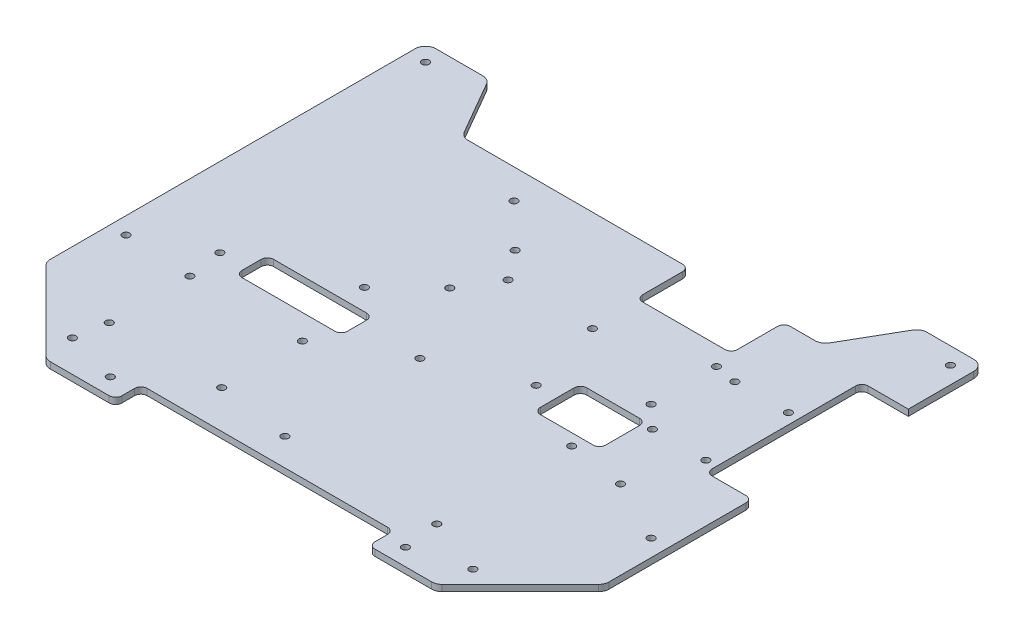
SolidWorks part; units mm, degrees
material "Acier non allié"
ref_plane "Front" through (0, 0, 0) normal (0, 0, 1) x (1, 0, 0)
ref_plane "Top" through (0, 0, 0) normal (0, 1, 0) x (1, 0, 0)
ref_plane "Right" through (0, 0, 0) normal (1, 0, 0) x (0, 0, -1)
sketch "Esquisse1" plane through (0, 0, 0) normal (0, 1, 0) x (1, 0, 0)
  line L0 (0, 0) -> (0, 190) construction
  line L1 (-92.5, 0) -> (92.5, 0)
  line L2 (92.5, 0) -> (132.5, 40)
  line L3 (132.5, 40) -> (132.5, 220)
  line L4 (132.5, 220) -> (102.5, 220)
  line L5 (102.5, 220) -> (85.1795, 190)
  line L6 (85.1795, 190) -> (-85.1795, 190)
  line L7 (-102.5, 220) -> (-85.1795, 190)
  line L8 (-132.5, 220) -> (-102.5, 220)
  line L9 (-132.5, 40) -> (-132.5, 220)
  line L10 (-92.5, 0) -> (-132.5, 40)
  dimension "D1" = 132.5
  dimension "D2" = 220
  dimension "D3" = 60
  dimension "D4" = 30
  dimension "D5" = 40
  dimension "D6" = 40
  dimension "D7" = 30
extrude "Boss.-Extru.1" add sketch "Esquisse1" along normal blind 3
fillet "Congé1" radius 5 10 edges at (92.5, 1.5, 0) (132.5, 1.5, -40) (132.5, 1.5, -220) (102.5, 1.5, -220) (85.1795, 1.5, -190) (-85.1795, 1.5, -190) (-102.5, 1.5, -220) (-132.5, 1.5, -220) (-92.5, 1.5, 0) (-132.5, 1.5, -40)
sketch "Esquisse2" plane through (0, 3, 0) normal (0, 1, 0) x (1, 0, 0)
  line L0 (0, 0) -> (0, 294.1173) construction
  line L2 (-90.4289, 0) -> (90.4289, 0) construction
  circle A0 centre (70, 8) radius 1
  circle A1 centre (124.5, 70) radius 1
  circle A2 centre (124.5, 212) radius 1
  circle A3 centre (-124.5, 212) radius 1
  circle A4 centre (-124.5, 70) radius 1
  circle A5 centre (-70, 8) radius 1
  dimension "D2" = 2
  dimension "D6" = 2
  dimension "D9" = 2
  dimension "D1" = 70
  dimension "D3" = 8
  dimension "D4" = 124.5
  dimension "D5" = 70
  dimension "D7" = 124.5
  dimension "D8" = 212
extrude "Enlèv. mat.-Extru.1" cut sketch "Esquisse2" against normal blind 3
hole_wizard "Dégagement M31" positions "Esquisse3" profile "Esquisse4" hole size "M3" standard "ISO" end condition through all
sketch "Esquisse3" plane through (0, 3, 0) normal (0, 1, 0) x (1, 0, 0)
  point P0 (70, 8)
  point P3 (-70, 8)
  point P6 (-124.5, 70)
  point P9 (-124.5, 212)
  point P12 (124.5, 212)
  point P15 (124.5, 70)
sketch "Esquisse4" plane through (70, 3, -8) normal (1, 0, 0) x (0, 0, 1)
  line L0 (0, 0) -> (0, 3)
  line L1 (0, 3) -> (1.7, 3)
  line L2 (1.7, 3) -> (1.7, 0)
  line L5 (1.7, 0) -> (0, 0)
  line L11 (0, -6.35) -> (0, 107.95) construction
  dimension "Diamètre du perçage jusqu'au prochain" = 3.4
  dimension "Profondeur du perçage jusqu'au prochain" = 3
sketch "Esquisse5" plane through (0, 3, 0) normal (0, 1, 0) x (1, 0, 0)
  line L0 (82.2927, 190) -> (-82.2927, 190) construction
  line L1 (67.5, 190) -> (22.5, 190)
  line L2 (67.5, 190) -> (67.5, 165)
  line L3 (67.5, 165) -> (22.5, 165)
  line L4 (22.5, 190) -> (22.5, 165)
  line L5 (132.5, 42.0711) -> (132.5, 215) construction
  line L6 (132.5, 184) -> (110.5, 184)
  line L7 (132.5, 184) -> (132.5, 110)
  line L8 (132.5, 110) -> (110.5, 110)
  line L9 (110.5, 184) -> (110.5, 110)
  line L10 (127.5, 220) -> (105.3868, 220) construction
  dimension "D1" = 25
  dimension "D2" = 65
  dimension "D3" = 110
  dimension "D4" = 36
  dimension "D5" = 110
  dimension "D6" = 22
extrude "Enlèv. mat.-Extru.2" cut sketch "Esquisse5" against normal through all
fillet "Congé2" radius 3 7 edges at (132.5, 1.5, -110) (110.5, 1.5, -110) (110.5, 1.5, -184) (67.5, 1.5, -190) (67.5, 1.5, -165) (22.5, 1.5, -165) (22.5, 1.5, -190)
sketch "Esquisse6" plane through (0, 3, 0) normal (0, 1, 0) x (1, 0, 0)
  line L0 (110.5, 140.5) -> (-167.6757, 140.5) construction
  line L1 (110.5, 181) -> (110.5, 113) construction
  line L2 (-90.4289, 0) -> (90.4289, 0) construction
  line L3 (110.5, 181) -> (110.5, 113) construction
  circle A0 centre (69.5, 156) radius 1
  circle A1 centre (-26, 156) radius 1
  circle A2 centre (-46.5, 176) radius 1
  circle A3 centre (69.5, 125) radius 1
  circle A4 centre (-26, 125) radius 1
  circle A5 centre (-46.5, 105) radius 1
  dimension "D4" = 2
  dimension "D6" = 2
  dimension "D10" = 2
  dimension "D1" = 140.5
  dimension "D2" = 41
  dimension "D3" = 15.5
  dimension "D5" = 136.5
  dimension "D7" = 15.5
  dimension "D8" = 35.5
  dimension "D9" = 157
extrude "Enlèv. mat.-Extru.3" cut sketch "Esquisse6" against normal through all
hole_wizard "Dégagement M32" positions "Esquisse7" profile "Esquisse8" hole size "M3" standard "ISO"
sketch "Esquisse7" plane through (0, 3, 0) normal (0, 1, 0) x (1, 0, 0)
  point P0 (-46.5, 105)
  point P3 (-26, 125)
  point P6 (-26, 156)
  point P9 (-46.5, 176)
  point P12 (69.5, 156)
  point P15 (69.5, 125)
sketch "Esquisse8" plane through (-46.5, 3, -105) normal (1, 0, 0) x (0, 0, 1)
  line L0 (0, 0) -> (0, 11.0215)
  line L1 (0, 11.0215) -> (1.7, 10)
  line L2 (1.7, 10) -> (1.7, 0)
  line L5 (1.7, 0) -> (0, 0)
  line L10 (0, 11.0215) -> (-1.7, 10) construction
  line L11 (0, -6.35) -> (0, 107.95) construction
  dimension "Diamètre du perçage" = 3.4
  dimension "Profondeur du perçage" = 10
  dimension "Angle de pointe" = 118
sketch "Esquisse9" plane through (0, 3, 0) normal (0, 1, 0) x (1, 0, 0)
  line L0 (132.5, 42.0711) -> (132.5, 107) construction
  line L1 (-90.4289, 0) -> (90.4289, 0) construction
  line L2 (-132.5, 215) -> (-132.5, 42.0711) construction
  line L3 (-39.16, 30) -> (-92.5, 30) construction
  line L4 (-39.16, 30) -> (-39.16, 68.24) construction
  line L5 (-39.16, 68.24) -> (-92.5, 68.24) construction
  line L6 (-92.5, 30) -> (-92.5, 68.24) construction
  line L7 (-4.16, 25) -> (-4.16, 89) construction
  line L8 (25.5, 165) -> (64.5, 165) construction
  line L9 (24.5, 142.1606) -> (-15.5, 142.1606) construction
  line L10 (110.5, 181) -> (110.5, 113) construction
  line L11 (113.5, 110) -> (129.5, 110) construction
  circle A0 centre (105.5, 115) radius 1
  circle A3 centre (105.5, 154.12) radius 1
  circle A6 centre (-92.5, 68.24) radius 1
  circle A7 centre (-39.16, 68.24) radius 1
  circle A8 centre (-39.16, 30) radius 1
  circle A9 centre (-92.5, 30) radius 1
  circle A10 centre (-4.16, 89) radius 1
  circle A11 centre (67.84, 89) radius 1
  circle A12 centre (-4.16, 25) radius 1
  circle A13 centre (67.84, 25) radius 1
  circle A14 centre (-15.5, 142.1606) radius 1
  circle A15 centre (24.5, 142.1606) radius 1
  circle A16 centre (34.5, 105.5) radius 1
  circle A17 centre (80.1, 115) radius 1
  circle A18 centre (80.1, 154.12) radius 1
  dimension "D2" = 2
  dimension "D4" = 2
  dimension "D17" = 2
  dimension "D18" = 2
  dimension "D19" = 2
  dimension "D20" = 2
  dimension "D21" = 2
  dimension "D22" = 2
  dimension "D23" = 2
  dimension "D24" = 2
  dimension "D32" = 2
  dimension "D33" = 2
  dimension "D34" = 2
  dimension "D11" = 2
  dimension "D12" = 2
  dimension "D5" = 27
  dimension "25" = 27
  dimension "D10" = 39.12
  dimension "D13" = 38.24
  dimension "D14" = 53.34
  dimension "D15" = 30
  dimension "D16" = 40
  dimension "D25" = 72
  dimension "D26" = 72
  dimension "D27" = 64
  dimension "D28" = 64
  dimension "D29" = 35
  dimension "D30" = 25
  dimension "D31" = 25
  dimension "D36" = 38
  dimension "D37" = 40
  dimension "D39" = 10
  dimension "D7" = 5
  dimension "D8" = 25.4
  dimension "D9" = 25.4
  dimension "D40" = 39.12
  dimension "D35" = 59.5
  dimension "D38" = 76
extrude "Enlèv. mat.-Extru.4" cut sketch "Esquisse9" against normal through all
hole_wizard "Dégagement M33" positions "Esquisse10" profile "Esquisse11" hole size "M3" standard "ISO"
sketch "Esquisse10" plane through (0, 3, 0) normal (0, 1, 0) x (1, 0, 0)
  point P3 (105.5, 115)
  point P9 (105.5, 154.12)
  point P14 (80.1, 154.12)
  point P17 (80.1, 115)
sketch "Esquisse11" plane through (105.5, 3, -115) normal (1, 0, 0) x (0, 0, 1)
  line L0 (0, 0) -> (0, 11.0215)
  line L1 (0, 11.0215) -> (1.7, 10)
  line L2 (1.7, 10) -> (1.7, 0)
  line L5 (1.7, 0) -> (0, 0)
  line L10 (0, 11.0215) -> (-1.7, 10) construction
  line L11 (0, -6.35) -> (0, 107.95) construction
  dimension "Diamètre du perçage" = 3.4
  dimension "Profondeur du perçage" = 10
  dimension "Angle de pointe" = 118
sketch "Esquisse12" plane through (0, 3, 0) normal (0, 1, 0) x (1, 0, 0)
  line L2 (-90.4289, 0) -> (90.4289, 0) construction
  line L3 (95, 15) -> (-95, 15) construction
  line L4 (95, 15) -> (95, 85) construction
  line L5 (95, 85) -> (-95, 85) construction
  line L6 (-95, 15) -> (-95, 85) construction
  line L7 (132.5, 42.0711) -> (132.5, 107) construction
  circle A4 centre (-95, 85) radius 1
  circle A5 centre (95, 85) radius 1
  circle A6 centre (95, 15) radius 1
  circle A7 centre (-95, 15) radius 1
  point P6 (95, 50)
  dimension "D5" = 2
  dimension "D6" = 2
  dimension "D7" = 2
  dimension "D8" = 2
  dimension "D1" = 70
  dimension "D2" = 190
  dimension "D3" = 15
  dimension "D4" = 37.5
extrude "Enlèv. mat.-Extru.5" cut sketch "Esquisse12" against normal through all and the other way through all
hole_wizard "Dégagement M34" positions "Esquisse13" profile "Esquisse14" hole size "M3" standard "ISO"
sketch "Esquisse13" plane through (0, 3, 0) normal (0, 1, 0) x (1, 0, 0)
  point P3 (-92.5, 68.24)
  point P6 (-92.5, 30)
  point P9 (-39.16, 30)
  point P12 (-39.16, 68.24)
  point P16 (-4.16, 25)
  point P19 (67.84, 25)
  point P22 (-4.16, 89)
  point P25 (67.84, 89)
  point P29 (34.5, 105.5)
  point P32 (24.5, 142.1606)
  point P35 (-15.5, 142.1606)
sketch "Esquisse14" plane through (-92.5, 3, -68.24) normal (1, 0, 0) x (0, 0, 1)
  line L0 (0, 0) -> (0, 11.0215)
  line L1 (0, 11.0215) -> (1.7, 10)
  line L2 (1.7, 10) -> (1.7, 0)
  line L5 (1.7, 0) -> (0, 0)
  line L10 (0, 11.0215) -> (-1.7, 10) construction
  line L11 (0, -6.35) -> (0, 107.95) construction
  dimension "Diamètre du perçage" = 3.4
  dimension "Profondeur du perçage" = 10
  dimension "Angle de pointe" = 118
hole_wizard "Dégagement M35" positions "Esquisse15" profile "Esquisse16" hole size "M3" standard "ISO"
sketch "Esquisse15" plane through (0, 3, 0) normal (0, 1, 0) x (1, 0, 0)
  point P0 (-95, 15)
  point P3 (-95, 85)
  point P6 (95, 85)
  point P9 (95, 15)
sketch "Esquisse16" plane through (-95, 3, -15) normal (1, 0, 0) x (0, 0, 1)
  line L0 (0, 0) -> (0, 11.0215)
  line L1 (0, 11.0215) -> (1.7, 10)
  line L2 (1.7, 10) -> (1.7, 0)
  line L5 (1.7, 0) -> (0, 0)
  line L10 (0, 11.0215) -> (-1.7, 10) construction
  line L11 (0, -6.35) -> (0, 107.95) construction
  dimension "Diamètre du perçage" = 3.4
  dimension "Profondeur du perçage" = 10
  dimension "Angle de pointe" = 118
sketch "Esquisse17" plane through (0, 3, 0) normal (0, 1, 0) x (1, 0, 0)
  line L0 (-90.4289, 0) -> (90.4289, 0) construction
  line L1 (-82.5, 95) -> (-32.5, 95)
  line L2 (-82.5, 95) -> (-82.5, 80)
  line L3 (-82.5, 80) -> (-32.5, 80)
  line L4 (-32.5, 95) -> (-32.5, 80)
  line L5 (-132.5, 215) -> (-132.5, 42.0711) construction
  line L6 (132.5, 42.0711) -> (132.5, 107) construction
  line L7 (44.5, 116.5) -> (75.5, 116.5)
  line L8 (44.5, 116.5) -> (44.5, 94.5)
  line L9 (44.5, 94.5) -> (75.5, 94.5)
  line L10 (75.5, 116.5) -> (75.5, 94.5)
  line L11 (82.2927, 190) -> (70.5, 190) construction
  line L13 (-59.5, 12) -> (60.5, 12)
  line L14 (-59.5, 12) -> (-59.5, 0)
  line L15 (-59.5, 0) -> (60.5, 0)
  line L16 (60.5, 12) -> (60.5, 0)
  dimension "D1" = 50
  dimension "D2" = 15
  dimension "D3" = 80
  dimension "D4" = 50
  dimension "D5" = 31
  dimension "D6" = 22
  dimension "D7" = 57
  dimension "D8" = 73.5
  dimension "D9" = 12
  dimension "D11" = 120
  dimension "D12" = 72
extrude "Enlèv. mat.-Extru.6" cut sketch "Esquisse17" against normal up to surface (3 mm away) up to face at (-95, 0, -13.3)
fillet "Congé3" radius 3 12 edges at (60.5, 1.5, 0) (60.5, 1.5, -12) (-59.5, 1.5, -12) (-59.5, 1.5, 0) (44.5, 1.5, -116.5) (75.5, 1.5, -116.5) (75.5, 1.5, -94.5) (44.5, 1.5, -94.5) (-82.5, 1.5, -80) (-32.5, 1.5, -80) (-32.5, 1.5, -95) (-82.5, 1.5, -95)
equation "\"WIDTH\"= 300mm'Total width of the robot"
equation "\"LENGTH\"= 220mm'Total length of the robot"
equation "\"CUT_DEPTH\"= 45mm'Depth of the cut on the edges of the plate"
equation "\"Plate_th\"= 3mm'Thickness of the plate"
equation "\"D1\"= \"Plate_th\""
equation "\"D5@Esquisse9\"=\"25@Esquisse9\""
